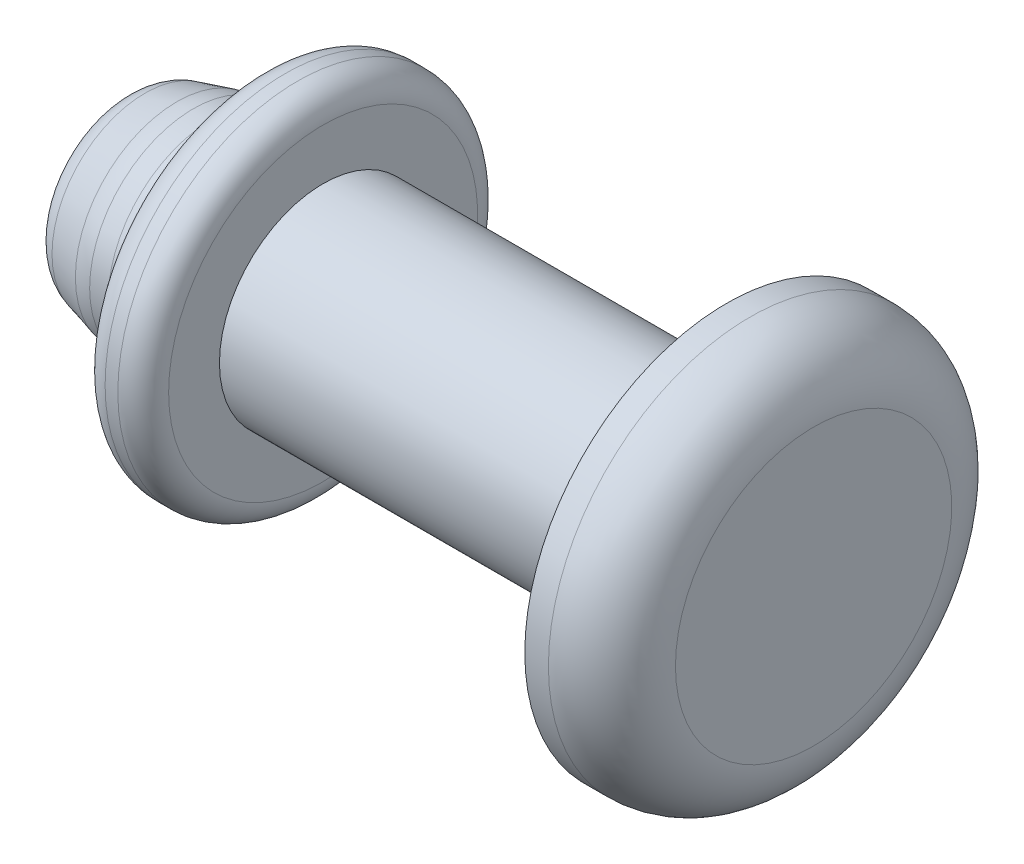
SolidWorks part; units mm, degrees
material "Ti-6Al-4VSolution treated and aged (SS)"
ref_plane "Front Plane" through (0, 0, 0) normal (0, 0, 1) x (1, 0, 0)
ref_plane "Top Plane" through (0, 0, 0) normal (0, 1, 0) x (1, 0, 0)
ref_plane "Right Plane" through (0, 0, 0) normal (1, 0, 0) x (0, 0, -1)
sketch "Sketch2" plane through (0, 0, 0) normal (0, 0, 1) x (1, 0, 0)
  line L0 (-42.3, 0) -> (42.3, 0) construction
  line L1 (0, 0) -> (0, 2.175)
  line L2 (-1, 3.175) -> (-1.3716, 3.175)
  line L3 (-1.3716, 3.175) -> (-1.3716, 1.632)
  line L4 (-1.3716, 1.632) -> (-7.7216, 1.6319)
  line L5 (-7.7216, 1.6319) -> (-7.7216, 2.4319)
  line L10 (-7.7216, 2.8319) -> (-7.7216, 0) construction
  line L11 (-1.3716, 3.175) -> (-1.3716, 0) construction
  line L12 (0, 0) -> (-10.8966, 0)
  line L15 (-8.1216, 2.8319) -> (-8.3216, 2.8319)
  line L16 (-8.7216, 2.4319) -> (-8.7216, 2.382)
  line L18 (-9.4716, 1.6319) -> (-9.7649, 1.6319)
  line L19 (-10.8966, 0.9803) -> (-10.8966, 0)
  line L20 (-10.0238, 1.5979) -> (-10.526, 1.4633)
  arc A0 (0, 2.175) -> (-1, 3.175) centre (-1, 2.175) ccw
  arc A6 (-8.7216, 2.4319) -> (-8.3216, 2.8319) centre (-8.3216, 2.4319) cw
  arc A7 (-7.7216, 2.4319) -> (-8.1216, 2.8319) centre (-8.1216, 2.4319) ccw
  arc A8 (-9.4716, 1.6319) -> (-8.7216, 2.382) centre (-9.4716, 2.3819) ccw
  arc A9 (-9.7649, 1.6319) -> (-10.0238, 1.5979) centre (-9.7649, 0.6319) ccw
  arc A10 (-10.8966, 0.9803) -> (-10.526, 1.4633) centre (-10.3966, 0.9803) cw
  point P4 (0, 0)
  point P14 (-10.8966, 1.6319)
  point P18 (0, 3.175)
  point P26 (0, 0)
  point P28 (0, 0)
  point P30 (-10.8966, 1.6319)
  point P33 (-9.8966, 1.6319)
  dimension "D9" = 1
  dimension "D13" = 0.4
  dimension "D16" = 0.75
  dimension "D14" = 1
  dimension "D15" = 0.5
  dimension "D2" = 3.175
  dimension "D3" = 1.632
  dimension "D4" = 6.35
  dimension "D5" = 1.3716
  dimension "D8" = 1.632
  dimension "D7" = 1.2
  dimension "D10" = 1
  dimension "D6" = 3.175
  dimension "D11" = 1
  dimension "D12" = 15
revolve "Revolve1" add sketch "Sketch2" angle 360 about L0
equation "\"Grip Length\"= 0.250in"
equation "\"Rivet Head Height\"= .054in"
equation "\"Rivet Head Radius\" = .250in / 2"
equation "\"Radius Shaft\"= 0.1285in'CHERRY CR1919-04"
equation "\"D2@Sketch2\"=\"Rivet Head Radius\""
equation "\"D3@Sketch2\"=\"Rivet Shank\""
equation "\"D4@Sketch2\"=\"Grip Length\""
equation "\"D5@Sketch2\"=\"Rivet Head Height\""
equation "\"Rivet Shank\"= 0.1285in / 2'CHERRY CR1919-04"
equation "\"D8@Sketch2\"=\"Rivet Shank\""
equation "\"D6@Sketch2\"=\"Grip Length\"/2"
